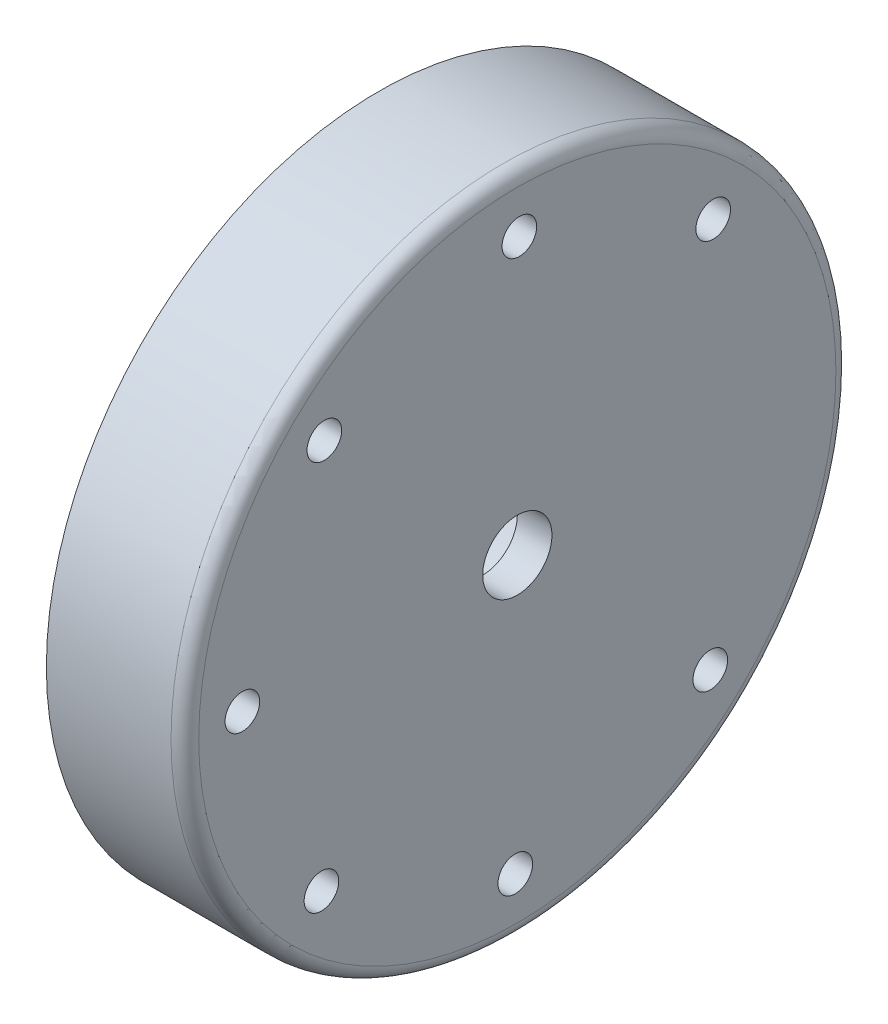
SolidWorks part; units mm, degrees
ref_plane "Front Plane" through (0, 0, 0) normal (0, 0, 1) x (1, 0, 0)
ref_plane "Top Plane" through (0, 0, 0) normal (0, 1, 0) x (1, 0, 0)
ref_plane "Right Plane" through (0, 0, 0) normal (1, 0, 0) x (0, 0, -1)
sketch "Sketch1" plane through (0, 0, 0) normal (1, 0, 0) x (0, 0, -1)
  circle A0 centre (0, 0) radius 60.96
extrude "Boss-Extrude1" add sketch "Sketch1" along normal blind 25.4
fillet "Fillet1" radius 2.54 1 edges at (25.4, 0, -60.96)
sketch "Sketch2" plane through (25.4, 0, 0) normal (1, 0, 0) x (0, 0, -1)
  circle A0 centre (0, 0) radius 4.05
extrude "Cut-Extrude1" cut sketch "Sketch2" against normal blind 6.35
sketch "Sketch3" plane through (25.4, 0, 0) normal (1, 0, 0) x (0, 0, -1)
  circle A0 centre (22.5439, 0) radius 3.175
extrude "Cut-Extrude2" [suppressed] cut sketch "Sketch3" against normal blind 19.05
pattern_circular "CirPattern1" [suppressed] count 8 over 360 of bodies 103
sketch "Sketch4" plane through (25.4, 0, 0) normal (1, 0, 0) x (0, 0, -1)
  circle A0 centre (0, 0) radius 25.019
extrude "Cut-Extrude3" cut sketch "Sketch4" against normal through all
sketch "Sketch5" plane through (0, 0, 0) normal (-1, 0, 0) x (0, 0, 1)
  circle A0 centre (-35.9173, 35.3839) radius 3.175
extrude "Cut-Extrude4" cut sketch "Sketch5" against normal through all contours A0
pattern_circular "CirPattern2" count 8 over 360 about axis through (25.4, 0, 0) along (1, 0, 0) skipping 7 of "Cut-Extrude4"
sketch "Sketch6" plane through (25.4, 0, 0) normal (1, 0, 0) x (0, 0, -1)
  circle A0 centre (0, 0) radius 25.019
  circle A1 centre (0, 0) radius 6.35
extrude "Boss-Extrude2" add sketch "Sketch6" against normal blind 6.35
